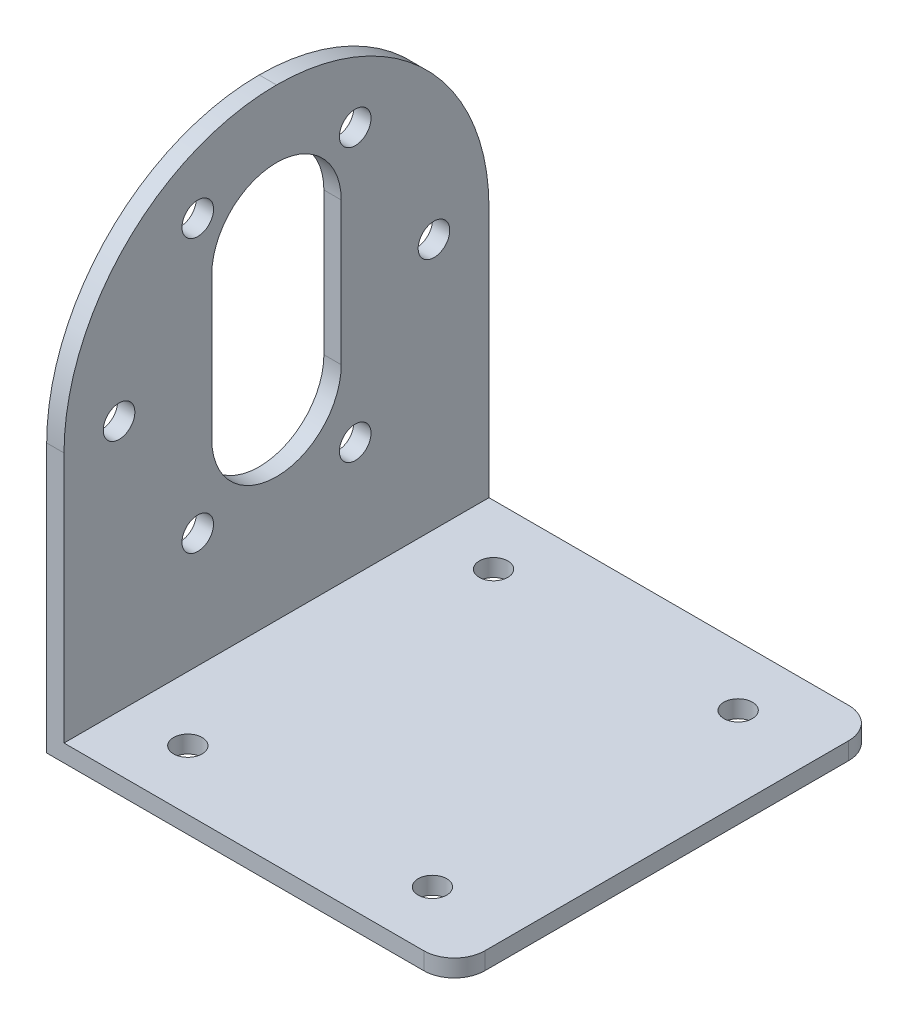
SolidWorks part; units mm, degrees
material "Aleación 6061"
ref_plane "Alzado" through (0, 0, 0) normal (0, 0, 1) x (1, 0, 0)
ref_plane "Planta" through (0, 0, 0) normal (0, 1, 0) x (1, 0, 0)
ref_plane "Vista lateral" through (0, 0, 0) normal (1, 0, 0) x (0, 0, -1)
sketch "Croquis1" plane through (0, 0, 0) normal (0, 1, 0) x (1, 0, 0)
  line L0 (0, 0) -> (0, 35.9627) construction
  line L1 (-20, -20.85) -> (17, -20.85)
  line L2 (-20, -20.85) -> (-20, 20.85)
  line L3 (-20, 20.85) -> (17, 20.85)
  line L4 (20, -17.85) -> (20, 17.85)
  line L5 (-20, -20.85) -> (20, 20.85) construction
  line L6 (-20, 20.85) -> (20, -20.85) construction
  line L7 (0, 0) -> (28.6957, 0) construction
  arc A0 (17, -20.85) -> (20, -17.85) centre (17, -17.85) ccw
  arc A1 (17, 20.85) -> (20, 17.85) centre (17, 17.85) cw
  circle A2 centre (-12, 15) radius 1.4
  circle A3 centre (12, 15) radius 1.4
  circle A4 centre (12, -15) radius 1.4
  circle A5 centre (-12, -15) radius 1.4
  point P0 (0, 0)
  dimension "D3" = 3
  dimension "D4" = 2.8
  dimension "D1" = 40
  dimension "D2" = 41.7
  dimension "24" = 24
  dimension "D5" = 12
  dimension "D6" = 30
  dimension "D7" = 15
extrude "Saliente-Extruir1" add sketch "Croquis1" along normal blind 1.7
sketch "Croquis2" plane through (0, 1.7, 0) normal (0, 1, 0) x (1, 0, 0)
  line L0 (-20, -20.85) -> (17, -20.85) construction
  line L1 (-20, 20.85) -> (-18.3, 20.85)
  line L2 (-20, 20.85) -> (-20, -20.85)
  line L3 (-20, -20.85) -> (-18.3, -20.85)
  line L4 (-18.3, 20.85) -> (-18.3, -20.85)
  dimension "D1" = 1.7
extrude "Saliente-Extruir2" add sketch "Croquis2" along normal blind 45.5
fillet "Redondeo1" radius 20.85 2 edges at (-19.15, 47.2, -20.85) (-19.15, 47.2, 20.85)
sketch "Croquis3" plane through (-18.3, 0, 0) normal (1, 0, 0) x (0, 0, -1)
  line L0 (0, 34.25) -> (0, 20.25) construction
  line L1 (6.35, 34.25) -> (6.35, 20.25)
  line L2 (-6.35, 34.25) -> (-6.35, 20.25)
  line L3 (0, 26.35) -> (15.45, 26.35) construction
  line L4 (0, 47.2) -> (0, 0) construction
  arc A0 (6.35, 34.25) -> (-6.35, 34.25) centre (0, 34.25) ccw
  arc A1 (-6.35, 20.25) -> (6.35, 20.25) centre (0, 20.25) ccw
  circle A2 centre (15.45, 26.35) radius 1.55
  circle A3 centre (7.725, 12.9699) radius 1.55
  circle A4 centre (-7.725, 12.9699) radius 1.55
  circle A5 centre (-15.45, 26.35) radius 1.55
  circle A6 centre (-7.725, 39.7301) radius 1.55
  circle A7 centre (7.725, 39.7301) radius 1.55
  point P3 (0, 27.25)
  point P8 (0, 40.6)
  point P9 (0, 13.9)
  point P28 (0, 26.35)
  dimension "D1" = 6.35
  dimension "D4" = 26.35
  dimension "D5" = 3.1
  dimension "D2" = 26.7
  dimension "D3" = 6.6
  dimension "D6" = 15.45
  dimension "D7" = 6
extrude "Cortar-Extruir1" cut sketch "Croquis3" against normal through all
